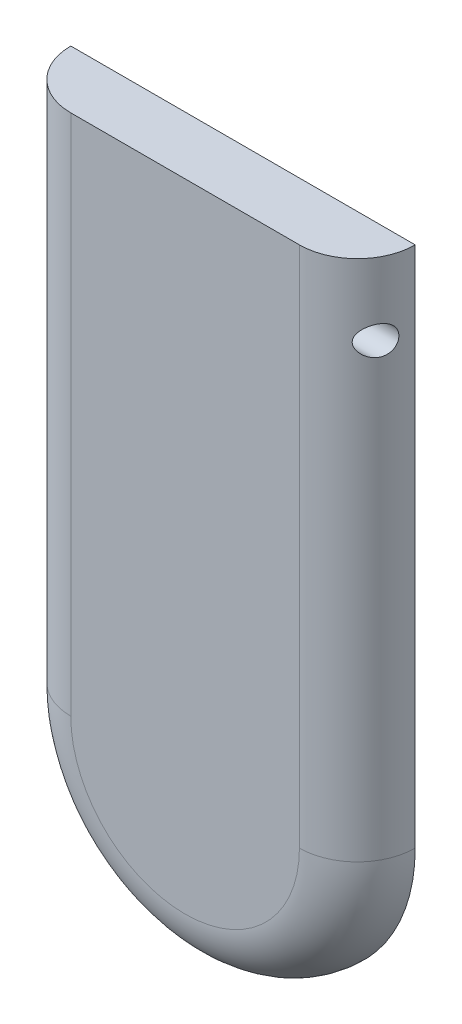
SolidWorks part; units mm, degrees
ref_plane "Спереди" through (0, 0, 0) normal (0, 0, 1) x (1, 0, 0)
ref_plane "Сверху" through (0, 0, 0) normal (0, 1, 0) x (1, 0, 0)
ref_plane "Справа" through (0, 0, 0) normal (1, 0, 0) x (0, 0, -1)
sketch "Эскиз1" plane through (0, 0, 0) normal (0, 0, 1) x (1, 0, 0)
  line L0 (0, 0) -> (59.5, 0)
  line L1 (59.5, 0) -> (59.5, -90.25)
  line L2 (0, 0) -> (0, -90.25)
  arc A0 (0, -90.25) -> (59.5, -90.25) centre (29.75, -90.25) ccw
  point P3 (29.75, 0)
  point P6 (29.75, -120)
  dimension "D1" = 59.5
  dimension "D2" = 120
extrude "Бобышка-Вытянуть1" add sketch "Эскиз1" along normal blind 10 contours L2 A0 L1 L0
sketch "Эскиз9" plane through (59.5, 0, 0) normal (1, 0, 0) x (0, 0, -1)
  line L0 (-10, 0) -> (0, 0) construction
  line L1 (0, 0) -> (0, -90.25) construction
  circle A0 centre (-5, -12.5) radius 2.5
  point P2 (0, 0)
  dimension "D1" = 5
  dimension "D2" = 12.5
  dimension "D3" = 5
extrude "Вырез-Вытянуть1" cut sketch "Эскиз9" against normal blind 59.5
fillet "Скругление3" radius 10 3 edges at (0, -45.125, 10) (59.5, -45.125, 10) (29.75, -120, 10)
